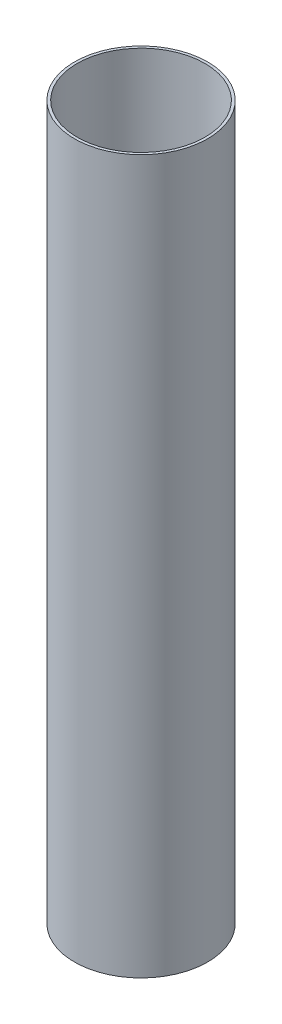
SolidWorks part; units mm, degrees
material "Thornel Mat VMA"
ref_plane "Front Plane" through (0, 0, 0) normal (0, 0, 1) x (1, 0, 0)
ref_plane "Top Plane" through (0, 0, 0) normal (0, 1, 0) x (1, 0, 0)
ref_plane "Right Plane" through (0, 0, 0) normal (1, 0, 0) x (0, 0, -1)
sketch "Sketch1" plane through (0, 0, 0) normal (0, 1, 0) x (1, 0, 0)
  circle A0 centre (0, 0) radius 27.3304
  circle A1 centre (0, 0) radius 28.4734
  dimension "D1" = 56.9468
  dimension "D2" = 54.6608
extrude "Boss-Extrude1" add sketch "Sketch1" along normal blind 304.8
